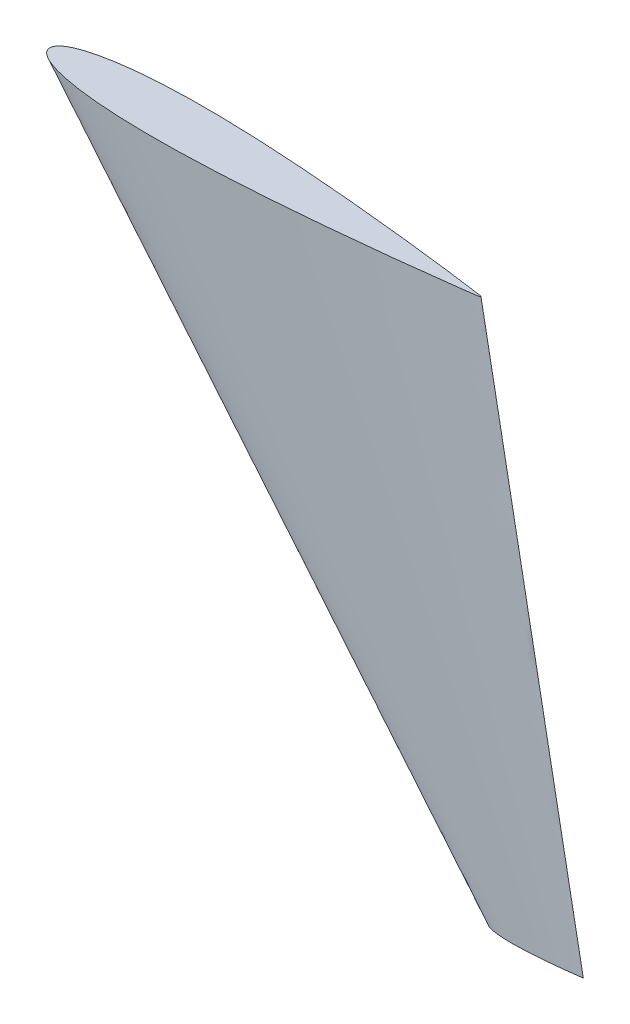
SolidWorks part; units mm, degrees
ref_plane "Front Plane" through (0, 0, 0) normal (0, 0, 1) x (1, 0, 0)
ref_plane "Top Plane" through (0, 0, 0) normal (0, 1, 0) x (1, 0, 0)
ref_plane "Right Plane" through (0, 0, 0) normal (1, 0, 0) x (0, 0, -1)
curve "Curve1"
  spline degree 3 poles (989.1889, 0, -3.124) (1003.9656, 0, 0) (989.1889, 0, 3.124) (979.4957, 0, 3.9602) (962.3964, 0, 6.4841) (943.9428, 0, 8.8491) (922.9132, 0, 11.6051) (900.2887, 0, 14.4478) (876.1894, 0, 17.4113) (850.9063, 0, 20.4351) (824.6249, 0, 23.4743) (797.5193, 0, 26.5234) (769.735, 0, 29.5334) (741.4059, 0, 32.5134) (712.6526, 0, 35.4198) (683.5857, 0, 38.2366) (654.3085, 0, 40.9505) (624.9168, 0, 43.5692) (595.4919, 0, 46.0176) (566.1196, 0, 48.3457) (536.8752, 0, 50.4873) (507.8364, 0, 52.4785) (479.0688, 0, 54.2437) (450.6418, 0, 55.8057) (422.6181, 0, 57.149) (395.0577, 0, 58.2561) (368.0197, 0, 59.0905) (341.5624, 0, 59.6944) (315.7376, 0, 59.999) (290.5993, 0, 60.0553) (266.1976, 0, 59.7899) (242.5818, 0, 59.2641) (219.7995, 0, 58.4267) (197.8965, 0, 57.3046) (176.9228, 0, 55.8955) (156.9193, 0, 54.1908) (137.9264, 0, 52.2182) (119.9888, 0, 49.9445) (103.1457, 0, 47.4173) (87.4377, 0, 44.6503) (72.9094, 0, 41.6113) (59.5881, 0, 38.3545) (47.5124, 0, 34.8789) (36.7185, 0, 31.1996) (27.2445, 0, 27.3184) (19.1092, 0, 23.264) (12.343, 0, 19.027) (6.9689, 0, 14.6049) (3.0199, 0, 9.972) (0.5665, 0, 5.0849) (-0.2745, 0, 0) (0.5665, 0, -5.0849) (3.0199, 0, -9.972) (6.9689, 0, -14.6049) (12.343, 0, -19.027) (19.1092, 0, -23.264) (27.2445, 0, -27.3184) (36.7185, 0, -31.1996) (47.5124, 0, -34.8789) (59.5881, 0, -38.3545) (72.9094, 0, -41.6113) (87.4377, 0, -44.6503) (103.1457, 0, -47.4173) (119.9888, 0, -49.9445) (137.9264, 0, -52.2182) (156.9193, 0, -54.1908) (176.9228, 0, -55.8955) (197.8965, 0, -57.3046) (219.7995, 0, -58.4267) (242.5818, 0, -59.2641) (266.1976, 0, -59.7899) (290.5993, 0, -60.0553) (315.7376, 0, -59.999) (341.5624, 0, -59.6944) (368.0197, 0, -59.0905) (395.0577, 0, -58.2561) (422.6181, 0, -57.149) (450.6418, 0, -55.8057) (479.0688, 0, -54.2437) (507.8364, 0, -52.4785) (536.8752, 0, -50.4873) (566.1196, 0, -48.3457) (595.4919, 0, -46.0176) (624.9168, 0, -43.5692) (654.3085, 0, -40.9505) (683.5857, 0, -38.2366) (712.6526, 0, -35.4198) (741.4059, 0, -32.5134) (769.735, 0, -29.5334) (797.5193, 0, -26.5234) (824.6249, 0, -23.4743) (850.9063, 0, -20.4351) (876.1894, 0, -17.4113) (900.2887, 0, -14.4478) (922.9132, 0, -11.6051) (943.9428, 0, -8.8491) (962.3964, 0, -6.4841) (979.4957, 0, -3.9602) (989.1889, 0, -3.124) (1003.9656, 0, 0) (989.1889, 0, 3.124) knots -0.01819 -0.010091 -0.003701 0 0.003701 0.010091 0.01819 0.027571 0.037978 0.04922 0.061159 0.073676 0.086676 0.10007 0.113795 0.12778 0.141967 0.156301 0.170733 0.185213 0.199702 0.214161 0.22855 0.24283 0.256971 0.270941 0.284704 0.298236 0.311509 0.32449 0.337159 0.349495 0.361463 0.373051 0.384237 0.394993 0.405307 0.415153 0.424519 0.43339 0.441745 0.449568 0.456846 0.463572 0.469733 0.475323 0.480337 0.484781 0.488676 0.492055 0.49498 0.497567 0.5 0.502433 0.50502 0.507945 0.511324 0.515219 0.519663 0.524677 0.530267 0.536428 0.543154 0.550432 0.558255 0.56661 0.575481 0.584847 0.594693 0.605007 0.615763 0.626949 0.638537 0.650505 0.662841 0.67551 0.688491 0.701764 0.715296 0.729059 0.743029 0.75717 0.77145 0.785839 0.800298 0.814787 0.829267 0.843699 0.858033 0.87222 0.886205 0.89993 0.913324 0.926324 0.938841 0.95078 0.962022 0.972429 0.98181 0.989909 0.996299 1 1.003701 1.010091 1.01819 periodic
sketch "Sketch2" plane through (0, 0, 0) normal (0, 1, 0) x (1, 0, 0)
  line L0 (8000, 0) -> (0, 0) construction
  line L1 (0, 0) -> (0, 395.0757) construction
  spline S1 degree 3 poles (7913.5111, -24.9917) (8031.7244, 0) (7913.5111, 24.9917) (7835.9656, 31.6818) (7699.1714, 51.8731) (7551.5421, 70.7926) (7383.3058, 92.8411) (7202.3097, 115.5825) (7009.5155, 139.2903) (6807.2507, 163.4811) (6596.999, 187.7941) (6380.1543, 212.1874) (6157.8798, 236.2671) (5931.2469, 260.1076) (5701.2206, 283.358) (5468.6854, 305.8929) (5234.4683, 327.6039) (4999.3345, 348.5532) (4763.9351, 368.1406) (4528.9569, 386.7656) (4295.002, 403.8987) (4062.6912, 419.8279) (3832.5502, 433.9494) (3605.1341, 446.4459) (3380.9452, 457.1923) (3160.4615, 466.0486) (2944.1578, 472.7239) (2732.499, 477.5553) (2525.9006, 479.9923) (2324.7946, 480.442) (2129.581, 478.3189) (1940.6547, 474.1131) (1758.3957, 467.4132) (1583.1723, 458.4372) (1415.3822, 447.1637) (1255.3541, 433.5267) (1103.4111, 417.7455) (959.9104, 399.5558) (825.1655, 379.3384) (699.5013, 357.2026) (583.2749, 332.8904) (476.7045, 306.8362) (380.0992, 279.0311) (293.7477, 249.5968) (217.9557, 218.5468) (152.8739, 186.1121) (98.7444, 152.2163) (55.7515, 116.8395) (24.1594, 79.7757) (4.532, 40.6789) (-2.1961, 0) (4.532, -40.6789) (24.1594, -79.7757) (55.7515, -116.8395) (98.7444, -152.2163) (152.8739, -186.1121) (217.9557, -218.5468) (293.7477, -249.5968) (380.0992, -279.0311) (476.7045, -306.8362) (583.2749, -332.8904) (699.5013, -357.2026) (825.1655, -379.3384) (959.9104, -399.5558) (1103.4111, -417.7455) (1255.3541, -433.5267) (1415.3822, -447.1637) (1583.1723, -458.4372) (1758.3957, -467.4132) (1940.6547, -474.1131) (2129.581, -478.3189) (2324.7946, -480.442) (2525.9006, -479.9923) (2732.499, -477.5553) (2944.1578, -472.7239) (3160.4615, -466.0486) (3380.9452, -457.1923) (3605.1341, -446.4459) (3832.5502, -433.9494) (4062.6912, -419.8279) (4295.002, -403.8987) (4528.9569, -386.7656) (4763.9351, -368.1406) (4999.3345, -348.5532) (5234.4683, -327.6039) (5468.6854, -305.8929) (5701.2206, -283.358) (5931.2469, -260.1076) (6157.8798, -236.2671) (6380.1543, -212.1874) (6596.999, -187.7941) (6807.2507, -163.4811) (7009.5155, -139.2903) (7202.3097, -115.5825) (7383.3058, -92.8411) (7551.5421, -70.7926) (7699.1714, -51.8731) (7835.9656, -31.6818) (7913.5111, -24.9917) (8031.7244, 0) (7913.5111, 24.9917) knots -0.01819 -0.010091 -0.003701 0 0.003701 0.010091 0.01819 0.027571 0.037978 0.04922 0.061159 0.073676 0.086676 0.10007 0.113795 0.12778 0.141967 0.156301 0.170733 0.185213 0.199702 0.214161 0.22855 0.24283 0.256971 0.270941 0.284704 0.298236 0.311509 0.32449 0.337159 0.349495 0.361463 0.373051 0.384237 0.394993 0.405307 0.415153 0.424519 0.43339 0.441745 0.449568 0.456846 0.463572 0.469733 0.475323 0.480337 0.484781 0.488676 0.492055 0.49498 0.497567 0.5 0.502433 0.50502 0.507945 0.511324 0.515219 0.519663 0.524677 0.530267 0.536428 0.543154 0.550432 0.558255 0.56661 0.575481 0.584847 0.594693 0.605007 0.615763 0.626949 0.638537 0.650505 0.662841 0.67551 0.688491 0.701764 0.715296 0.729059 0.743029 0.75717 0.77145 0.785839 0.800298 0.814787 0.829267 0.843699 0.858033 0.87222 0.886205 0.89993 0.913324 0.926324 0.938841 0.95078 0.962022 0.972429 0.98181 0.989909 0.996299 1 1.003701 1.010091 1.01819 only from (8000, 0) to (8000, 0)
  dimension "D1" = 8000
ref_plane "Plane1" through (0, -10000, 0) normal (0, 1, 0) x (1, 0, 0)
sketch "Sketch6" plane through (0, -10000, 0) normal (0, 1, 0) x (1, 0, 0)
  line L0 (9900, 0) -> (8150, 0) construction
  line L1 (8150, 0) -> (8150, 213.2137) construction
  line L2 (8000, 0) -> (0, 0) construction
  spline S1 degree 3 poles (9881.0805, -5.4669) (9906.9397, 0) (9881.0805, 5.4669) (9864.1175, 6.9304) (9834.1938, 11.3472) (9801.8998, 15.4859) (9765.0981, 20.309) (9725.5052, 25.2837) (9683.3315, 30.4697) (9639.0861, 35.7615) (9593.0935, 41.08) (9545.6587, 46.416) (9497.0362, 51.6834) (9447.4603, 56.8985) (9397.142, 61.9846) (9346.2749, 66.9141) (9295.0399, 71.6633) (9243.6044, 76.246) (9192.1108, 80.5308) (9140.7093, 84.605) (9089.5317, 88.3528) (9038.7137, 91.8374) (8988.3704, 94.9264) (8938.6231, 97.66) (8889.5818, 100.0108) (8841.3509, 101.9481) (8794.0345, 103.4083) (8747.7342, 104.4652) (8702.5408, 104.9983) (8658.5488, 105.0967) (8615.8458, 104.6323) (8574.5182, 103.7122) (8534.6491, 102.2466) (8496.3189, 100.2831) (8459.6149, 97.8171) (8424.6087, 94.834) (8391.3712, 91.3818) (8359.9804, 87.4028) (8330.505, 82.9803) (8303.0159, 78.1381) (8277.5914, 72.8198) (8254.2791, 67.1204) (8233.1467, 61.038) (8214.2573, 54.5993) (8197.6778, 47.8071) (8183.4412, 40.712) (8171.6003, 33.2973) (8162.1956, 25.5586) (8155.2849, 17.4509) (8150.9914, 8.8985) (8149.5196, 0) (8150.9914, -8.8985) (8155.2849, -17.4509) (8162.1956, -25.5586) (8171.6003, -33.2973) (8183.4412, -40.712) (8197.6778, -47.8071) (8214.2573, -54.5993) (8233.1467, -61.038) (8254.2791, -67.1204) (8277.5914, -72.8198) (8303.0159, -78.1381) (8330.505, -82.9803) (8359.9804, -87.4028) (8391.3712, -91.3818) (8424.6087, -94.834) (8459.6149, -97.8171) (8496.3189, -100.2831) (8534.6491, -102.2466) (8574.5182, -103.7122) (8615.8458, -104.6323) (8658.5488, -105.0967) (8702.5408, -104.9983) (8747.7342, -104.4652) (8794.0345, -103.4083) (8841.3509, -101.9481) (8889.5818, -100.0108) (8938.6231, -97.66) (8988.3704, -94.9264) (9038.7137, -91.8374) (9089.5317, -88.3528) (9140.7093, -84.605) (9192.1108, -80.5308) (9243.6044, -76.246) (9295.0399, -71.6633) (9346.2749, -66.9141) (9397.142, -61.9846) (9447.4603, -56.8985) (9497.0362, -51.6834) (9545.6587, -46.416) (9593.0935, -41.08) (9639.0861, -35.7615) (9683.3315, -30.4697) (9725.5052, -25.2837) (9765.0981, -20.309) (9801.8998, -15.4859) (9834.1938, -11.3472) (9864.1175, -6.9304) (9881.0805, -5.4669) (9906.9397, 0) (9881.0805, 5.4669) knots -0.01819 -0.010091 -0.003701 0 0.003701 0.010091 0.01819 0.027571 0.037978 0.04922 0.061159 0.073676 0.086676 0.10007 0.113795 0.12778 0.141967 0.156301 0.170733 0.185213 0.199702 0.214161 0.22855 0.24283 0.256971 0.270941 0.284704 0.298236 0.311509 0.32449 0.337159 0.349495 0.361463 0.373051 0.384237 0.394993 0.405307 0.415153 0.424519 0.43339 0.441745 0.449568 0.456846 0.463572 0.469733 0.475323 0.480337 0.484781 0.488676 0.492055 0.49498 0.497567 0.5 0.502433 0.50502 0.507945 0.511324 0.515219 0.519663 0.524677 0.530267 0.536428 0.543154 0.550432 0.558255 0.56661 0.575481 0.584847 0.594693 0.605007 0.615763 0.626949 0.638537 0.650505 0.662841 0.67551 0.688491 0.701764 0.715296 0.729059 0.743029 0.75717 0.77145 0.785839 0.800298 0.814787 0.829267 0.843699 0.858033 0.87222 0.886205 0.89993 0.913324 0.926324 0.938841 0.95078 0.962022 0.972429 0.98181 0.989909 0.996299 1 1.003701 1.010091 1.01819 only from (9900, 0) to (9900, 0)
  point P1 (8150, 0)
  dimension "D1" = 1750
  dimension "D2" = 8150
loft "Loft4" add profiles "Sketch6", "Sketch2" connector at (9898.3769, -10000, 1.2968) connector at (7999.9313, 0, 0.5436)
